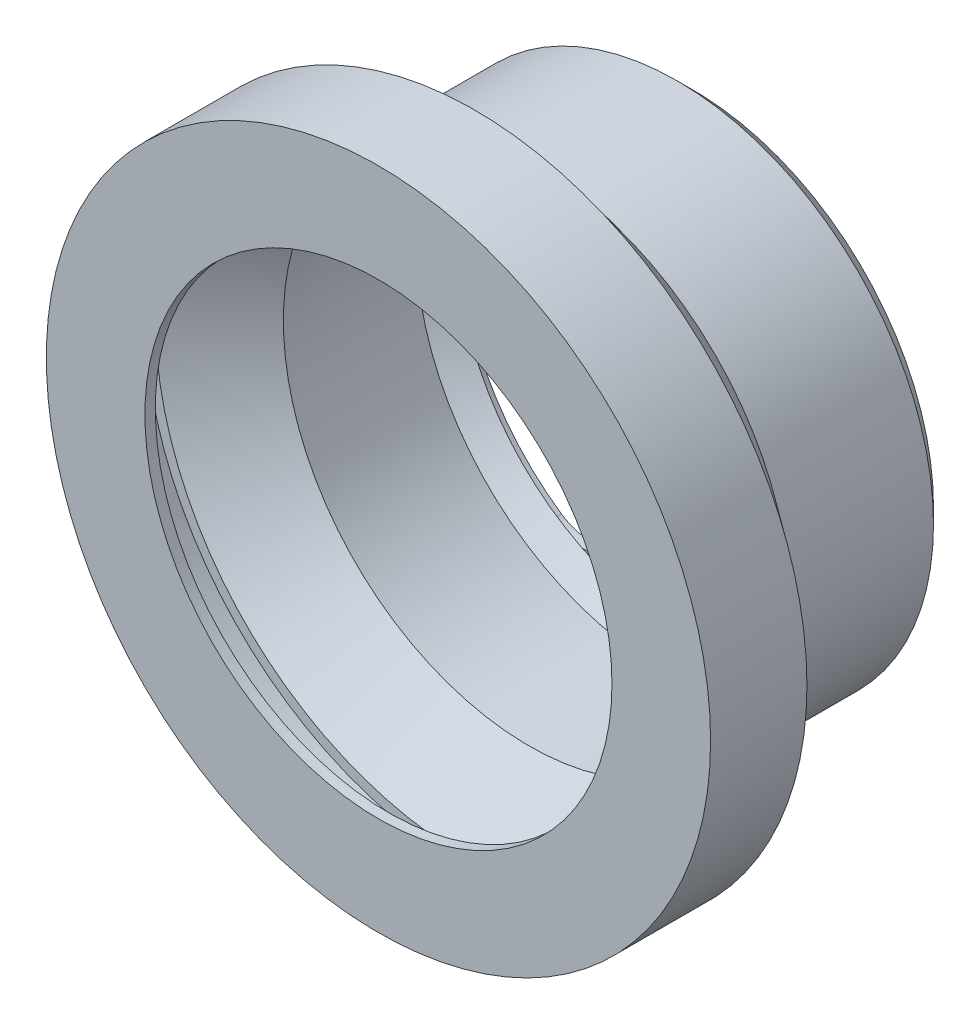
SolidWorks part; units mm, degrees
material "PET"
ref_plane "Front Plane" through (0, 0, 0) normal (0, 0, 1) x (1, 0, 0)
ref_plane "Top Plane" through (0, 0, 0) normal (0, 1, 0) x (1, 0, 0)
ref_plane "Right Plane" through (0, 0, 0) normal (1, 0, 0) x (0, 0, -1)
sketch "Sketch2" plane through (0, 0, 0) normal (1, 0, 0) x (0, 0, -1)
  line L0 (-1, 0) -> (92.0168, 0) construction
  line L1 (-1, 13.5) -> (-1, -13.5) construction
  line L2 (65.6, 47.35) -> (37, 47.35)
  line L3 (65.6, 49.35) -> (37, 49.35)
  line L4 (25.568, 64) -> (0, 64)
  line L5 (61, 45.35) -> (38, 45.35) construction
  line L6 (24, 62) -> (9, 62) construction
  line L7 (65.6, 47.35) -> (65.6, 49.35)
  line L8 (37, 42.15) -> (37, 39.076) construction
  line L9 (37, 49.35) -> (25.568, 64)
  line L10 (24, 62) -> (0, 62)
  line L11 (0, 62) -> (0, 64)
  line L12 (36.0238, 47.35) -> (37, 47.35)
  line L13 (36.0238, 47.35) -> (24, 60)
  line L14 (24, -62) -> (24, 62) construction
  line L15 (24, 60) -> (24, 62)
  line L16 (24.5918, 62) -> (0, 62) construction
  line L17 (35.4233, 48.1196) -> (24.5918, 62) construction
  dimension "D1" = 2
  dimension "D2" = 2
  dimension "D3" = 0
  dimension "D4" = 2
  dimension "D5" = 2
revolve "Revolve1" add sketch "Sketch2" angle 360 about L0
sketch "Sketch3" plane through (0, 0, -65.6) normal (0, 0, -1) x (-1, 0, 0)
  line L0 (22.5683, 1.9165) -> (14.1067, 0.046) construction
  line L1 (2.4267, -24.8762) -> (6.7436, -44.4048)
  line L2 (-23.5814, -8.2846) -> (-43.1099, -12.6015)
  line L3 (-24.8762, -2.4267) -> (-44.4048, -6.7436)
  line L4 (-8.2846, 23.5814) -> (-12.6015, 43.1099)
  line L5 (-2.4267, 24.8762) -> (-6.7436, 44.4048)
  line L6 (8.2846, -23.5814) -> (12.6015, -43.1099)
  line L7 (23.5814, 8.2846) -> (43.1099, 12.6015)
  line L9 (21.0718, -13.4422) -> (38.233, -24.3897) construction
  line L10 (24.8762, 2.4267) -> (44.4048, 6.7436)
  line L11 (5.9045, -12.8116) -> (7.775, -21.2732) construction
  arc A0 (23.5814, 8.2846) -> (-2.4267, 24.8762) centre (0, 0) ccw
  arc A1 (43.1099, 12.6015) -> (-6.7436, 44.4048) centre (0, 0) ccw
  circle A2 centre (-14.6464, -3.2377) radius 1.5
  circle A3 centre (-14.6464, -3.2377) radius 1.5
  circle A4 centre (3.2377, -14.6464) radius 1.5
  circle A5 centre (-3.2377, 14.6464) radius 1.5
  circle A6 centre (-3.2377, 14.6464) radius 1.5
  circle A7 centre (3.2377, -14.6464) radius 1.5
  circle A8 centre (14.6464, 3.2377) radius 1.5
  circle A9 centre (14.6464, 3.2377) radius 1.5
  arc A10 (-43.1099, -12.6015) -> (6.7436, -44.4048) centre (0, 0) ccw
  arc A11 (-23.5814, -8.2846) -> (2.4267, -24.8762) centre (0, 0) ccw
  arc A12 (12.6015, -43.1099) -> (44.4048, 6.7436) centre (0, 0) ccw
  arc A13 (8.2846, -23.5814) -> (24.8762, 2.4267) centre (0, 0) ccw
  arc A17 (-8.2846, 23.5814) -> (-24.8762, -2.4267) centre (0, 0) ccw
  circle A18 centre (0, 0) radius 45.35 construction
  circle A21 centre (0, 0) radius 49.35
  arc A22 (-12.6015, 43.1099) -> (-44.4048, -6.7436) centre (0, 0) ccw
  point P43 (0, 0)
  dimension "D5" = 180
  dimension "D6" = 20
  dimension "D7" = 20
  dimension "D8" = 0
  dimension "D1" = 0
  dimension "D2" = 0
  dimension "D3" = 0
  dimension "D4" = 0
  dimension "D9" = 4
extrude "Boss-Extrude2" add sketch "Sketch3" along normal blind 2
fillet "Fillet1" radius 10 4 edges at (-12.6015, -43.1099, -66.6) (-8.2846, -23.5814, -66.6) (-24.8762, 2.4267, -66.6) (-44.4048, 6.7436, -66.6)
fillet "Fillet2" radius 10 12 edges at (-43.1099, 12.6015, -66.6) (-23.5814, 8.2846, -66.6) (2.4267, 24.8762, -66.6) (6.7436, 44.4048, -66.6) (24.8762, -2.4267, -66.6) (44.4048, -6.7436, -66.6) (12.6015, 43.1099, -66.6) (8.2846, 23.5814, -66.6) (-6.7436, -44.4048, -66.6) (43.1099, -12.6015, -66.6) (23.5814, -8.2846, -66.6) (-2.4267, -24.8762, -66.6)
sketch "Sketch5" plane through (0, 0, 0) normal (0, 1, 0) x (1, 0, 0)
  line L0 (-47.35, 61.6) -> (-43.35, 65.6)
  line L1 (-44.4456, 65.6) -> (-32.3294, 65.6) construction
  line L2 (-47.35, 65.6) -> (47.35, 65.6) construction
  line L3 (-47.35, 61.6) -> (-47.35, 65.6)
  line L4 (-43.35, 65.6) -> (-47.35, 65.6)
  line L5 (0, 0) -> (0, 79.8548) construction
  dimension "D1" = 4
  dimension "D2" = 4
revolve "Revolve2" add sketch "Sketch5" angle 360 about L5
chamfer "Chamfer1" distance 3 angle 45 1 edges at (-49.35, 0, -67.6)
sketch "Sketch6" plane through (0, 0, 0) normal (0, 1, 0) x (1, 0, 0)
  line L0 (-64, 0) -> (64, 0) construction
  line L1 (64, 0) -> (-66.4041, 0)
  line L2 (64, 0) -> (64, 9)
  line L3 (64, 9) -> (-66.4041, 9)
  line L4 (-66.4041, 0) -> (-66.4041, 9)
  line L5 (-62, 9) -> (62, 9) construction
  dimension "D1" = 0
extrude "Cut-Extrude1" cut sketch "Sketch6" against normal mid plane 144
sketch "Sketch7" plane through (0, 0, -9) normal (0, 0, 1) x (1, 0, 0)
  circle A2 centre (0, 0) radius 45
  circle A3 centre (0, 0) radius 45
  circle A5 centre (0, 0) radius 64
  circle A6 centre (0, 0) radius 64
  dimension "D1" = 3
  dimension "D2" = 0
extrude "Boss-Extrude3" add sketch "Sketch7" along normal blind 2
